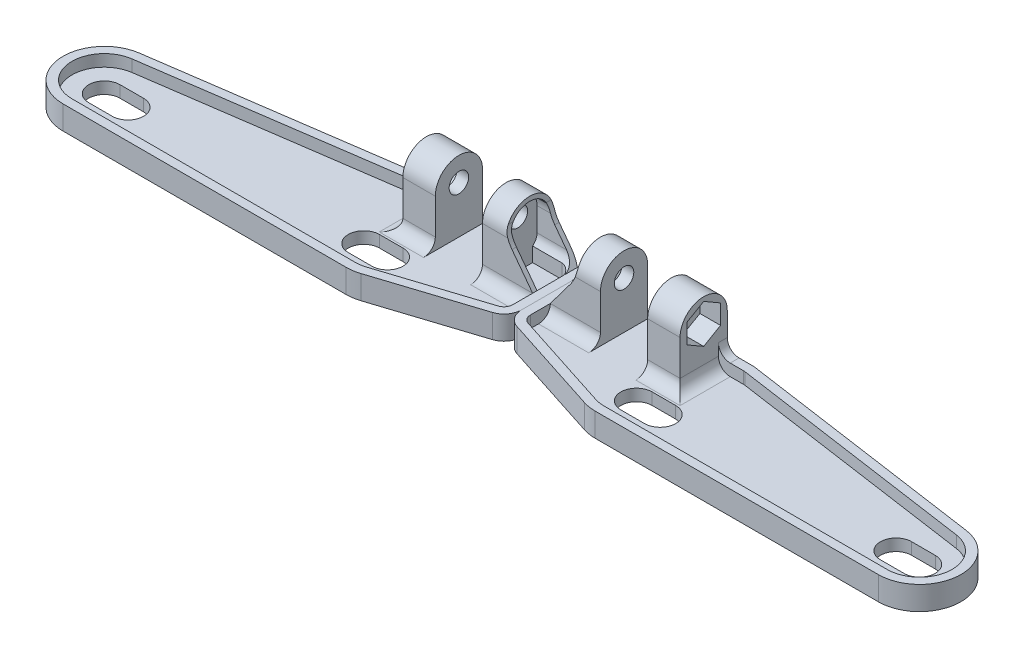
SolidWorks part; units mm, degrees
note: The reader was unsure of these and kept them because the rebuilt part matched: shared geometry of "Sketch2<3>".
ref_plane "Front Plane" through (0, 0, 0) normal (0, 0, 1) x (1, 0, 0)
ref_plane "Top Plane" through (0, 0, 0) normal (0, 1, 0) x (1, 0, 0)
ref_plane "Right Plane" through (0, 0, 0) normal (1, 0, 0) x (0, 0, -1)
sketch "Sketch2" plane through (0, 0, 0) normal (1, 0, 0) x (0, 0, -1)
  line L0 (4, 0) -> (4, -8)
  line L1 (4, -8) -> (-4, -8)
  line L2 (-4, -8) -> (-4, 0)
  line L4 (4, -8) -> (-16, -8)
  line L5 (4, -8) -> (4, -10)
  line L6 (4, -10) -> (-16, -10)
  line L7 (-16, -8) -> (-16, -10)
  circle A0 centre (0, 0) radius 4
  circle A1 centre (0, 0) radius 1.65
  dimension "D1" = 3.3
  dimension "D2" = 8
  dimension "D3" = 20
  dimension "D4" = 2
  dimension "D5" = 8
extrude "Boss-Extrude1" add sketch "Sketch2" along normal mid plane 12 contours A0 A1
sketch "Sketch18" plane through (0, 0, 0) normal (0, 1, 0) x (1, 0, 0)
  line L1 (-6, 106.0892) -> (-6, -15.5384) construction
  line L3 (-6, 1.65) -> (-6, -1.65) construction
  line L5 (-31.1122, 87.1949) -> (-31.1122, 25.8498) construction
extrude "Boss-Extrude2" add sketch "Sketch2<3>" along normal mid plane 12 from offset 0 contours A0 L2 L1 L0
sketch "Sketch2<3>" plane through (0, 0, 0) normal (1, 0, 0) x (0, 0, -1) same geometry as "Sketch2"
ref_plane "Plane2" through (0, -8, 0) normal (0, -1, 0) x (-1, 0, 0)
sketch "Sketch14" plane through (0, -8, 0) normal (0, 1, 0) x (1, 0, 0)
  line L0 (0, 4) -> (-14, 4)
  line L1 (6, 4) -> (-6, 4) construction
  line L2 (-31.1122, 87.1949) -> (-31.1122, 25.8498) construction
  line L4 (-31.1122, -9) -> (-31.1122, 4) construction
  line L5 (-31.1122, 4) -> (-14, 4) construction
  line L7 (-53.1122, -9) -> (-9.1122, -9) construction
  line L9 (-56.1111, -2.0716) -> (-14, 4)
  line L10 (-55.1122, -16) -> (-7.1122, -16)
  line L11 (-4.963, -15.6619) -> (14, -9.5443)
  line L12 (-55.1122, -9) -> (-51.1122, -9) construction
  line L13 (-55.1122, -6.35) -> (-51.1122, -6.35)
  line L14 (-55.1122, -11.65) -> (-51.1122, -11.65)
  line L15 (-7.1122, -9) -> (-11.1122, -9) construction
  line L16 (-7.1122, -11.65) -> (-11.1122, -11.65)
  line L17 (-7.1122, -6.35) -> (-11.1122, -6.35)
  line L19 (14, -9.5443) -> (14, 4)
  line L20 (14, 4) -> (-14, 4)
  circle A0 centre (-53.1122, -9) radius 2.65 construction
  circle A1 centre (-9.1122, -9) radius 2.65 construction
  arc A3 (-55.1122, -6.35) -> (-55.1122, -11.65) centre (-55.1122, -9) ccw
  arc A4 (-51.1122, -11.65) -> (-51.1122, -6.35) centre (-51.1122, -9) ccw
  arc A5 (-7.1122, -11.65) -> (-7.1122, -6.35) centre (-7.1122, -9) ccw
  arc A6 (-11.1122, -6.35) -> (-11.1122, -11.65) centre (-11.1122, -9) ccw
  circle A7 centre (-7.1122, -9) radius 7
  circle A8 centre (-55.1122, -9) radius 7
  point P15 (-31.1122, -9)
  point P28 (-53.1122, -9)
  point P35 (-9.1122, -9)
  dimension "D3" = 5.3
  dimension "14" = 14
  dimension "D1" = 8
  dimension "D2" = 44
  dimension "D4" = 13
  dimension "D6" = 4
  dimension "D7" = 4
  dimension "D9" = 8
extrude "Boss-Extrude7" add sketch "Sketch14" against normal blind 2 contours A7 A6 L17 A5 L16 | A7 A6 L16 A5 L17 | L10 A8 A4 L9 L0 L20 L19 L11 A7 A6
sketch "Sketch3" plane through (0, 0, 4) normal (0, 0, 1) x (1, 0, 0)
  line L1 (-4, 8) -> (4, 8)
  line L2 (-4, 8) -> (-4, -8)
  line L3 (-4, -8) -> (4, -8)
  line L4 (4, 8) -> (4, -8)
  line L5 (-4, 8) -> (4, -8) construction
  line L6 (-4, -8) -> (4, 8) construction
  line L7 (6, -8) -> (6, 0) construction
  point P0 (0, 0)
  dimension "D1" = 2
extrude "Cut-Extrude1" cut sketch "Sketch3" against normal blind 20
ref_plane "Plane1" through (0, 0, 0) normal (1, 0, 0) x (0, 0, -1)
sketch "Sketch8" plane through (6, 0, 0) normal (1, 0, 0) x (0, 0, -1)
  line L0 (-4, 0) -> (-4, -8)
  line L1 (-4, -8) -> (4, -8)
  line L2 (4, -8) -> (4, 0)
  line L4 (0, -3.3) -> (2.8579, -1.65)
  line L5 (2.8579, -1.65) -> (2.8579, 1.65)
  line L6 (2.8579, 1.65) -> (0, 3.3)
  line L7 (0, 3.3) -> (-2.8579, 1.65)
  line L8 (-2.8579, 1.65) -> (-2.8579, -1.65)
  line L9 (-2.8579, -1.65) -> (0, -3.3)
  circle A0 centre (0, 0) radius 4
  circle A1 centre (0, 0) radius 2.8579 construction
  dimension "D1" = 3.3
extrude "Boss-Extrude5" add sketch "Sketch8" against normal blind 3.5 from surface
sketch "Sketch11" plane through (-6, 0, 0) normal (-1, 0, 0) x (0, 0, 1)
  line L0 (-4, 0) -> (-4, -8)
  line L1 (-4, -8) -> (4, -8)
  line L2 (4, -8) -> (4, 0)
  line L3 (3.25, 0) -> (3.25, -8)
  line L4 (-3.25, 0) -> (-3.25, -8)
  circle A0 centre (0, 0) radius 3.25
  circle A1 centre (0, 0) radius 4
  dimension "D1" = 6.5
extrude "Boss-Extrude6" add sketch "Sketch11" against normal blind 8 from surface
sketch "Sketch12" plane through (0, 0, 4) normal (0, 0, 1) x (1, 0, 0)
  line L0 (4, 4) -> (8, 4)
  line L1 (14, 0) -> (14, 4) construction
  line L2 (8, 4) -> (8, 0)
  line L4 (8, 0) -> (14, -8)
  line L5 (14, -8) -> (14, 4)
  line L7 (14, 4) -> (8, 4)
  line L8 (14, 0) -> (14, -8) construction
  line L9 (14, -8) -> (12.5, -8) construction
  line L10 (14, -8) -> (4, -8) construction
  line L11 (12.5, -8) -> (12.5, -6) construction
  dimension "D1" = 4
  dimension "D2" = 1.5
  dimension "D3" = 2
extrude "Cut-Extrude2" cut sketch "Sketch12" against normal through all
fillet "Fillet1" radius 5 2 edges at (8, 0, 3.625) (8, 0, -3.625)
sketch "Sketch16" plane through (0, -10, 0) normal (0, -1, 0) x (1, 0, 0)
  line L0 (-51.1122, 11.65) -> (-55.1122, 6.35) construction
  line L1 (-11.1122, 11.65) -> (-7.1122, 6.35) construction
  line L2 (-7.1122, 9) -> (-11.1122, 9) construction
  line L3 (-51.1122, 9) -> (-55.1122, 9) construction
  point P12 (-9.1122, 9)
  point P16 (-53.1122, 9)
fillet "Fillet2" radius 3 3 edges at (14, -9, -4) (-14, -9, -4) (14, -9, 9.5443)
sketch "Sketch19" plane through (0, -8, 0) normal (0, 1, 0) x (1, 0, 0)
  line L0 (-14.213, 3.9693) -> (-56.1111, -2.0716)
  line L1 (-55.1122, -16) -> (-7.1122, -16)
  line L2 (-4.963, -15.6619) -> (11.9211, -10.215)
  line L3 (14, -7.3599) -> (14, 1)
  line L5 (11, 4) -> (-8.5211, 4)
  line L6 (-8.5211, 4) -> (-13.7848, 4)
  line L7 (-13.9989, 2.4846) -> (-55.897, -3.5563)
  line L8 (-55.1122, -14.5) -> (-7.1122, -14.5)
  line L9 (-5.4235, -14.2344) -> (11.4605, -8.7874)
  line L10 (12.5, -7.3599) -> (12.5, 1)
  line L11 (11, 2.5) -> (-8.5211, 2.5)
  line L12 (-8.5211, 2.5) -> (-13.7848, 2.5)
  arc A0 (-56.1111, -2.0716) -> (-55.1122, -16) centre (-55.1122, -9) ccw
  arc A1 (-7.1122, -16) -> (-4.963, -15.6619) centre (-7.1122, -9) ccw
  arc A2 (11.9211, -10.215) -> (14, -7.3599) centre (11, -7.3599) ccw
  arc A4 (14, 1) -> (11, 4) centre (11, 1) ccw
  arc A13 (-14.213, 3.9693) -> (-13.7848, 4) centre (-13.7848, 1) cw
  arc A14 (-55.897, -3.5563) -> (-55.1122, -14.5) centre (-55.1122, -9) ccw
  arc A15 (-7.1122, -14.5) -> (-5.4235, -14.2344) centre (-7.1122, -9) ccw
  arc A16 (11.4605, -8.7874) -> (12.5, -7.3599) centre (11, -7.3599) ccw
  arc A17 (12.5, 1) -> (11, 2.5) centre (11, 1) ccw
  arc A18 (-13.9989, 2.4846) -> (-13.7848, 2.5) centre (-13.7848, 1) cw
extrude "Boss-Extrude8" add sketch "Sketch19" along normal blind 2
fillet "Fillet3" radius 2 5 edges at (9.25, -6, -3.25) (-9.5, -8, 0.75) (-6.75, -8, 4) (8.25, -8, 4) (-9.5, -6, -3.25)
ref_plane "Plane3" through (-31.1122, 0, 0) normal (-1, 0, 0) x (0, 0, 1)
sketch "Sketch23" plane through (0, 0, -2.5) normal (0, 0, 1) x (1, 0, 0)
  line L0 (4, -8) -> (-4, -8) construction
  line L1 (-4, -6) -> (4, -6)
  line L2 (-4, -6) -> (-4, -8)
  line L3 (-4, -8) -> (4, -8)
  line L4 (4, -6) -> (4, -8)
extrude "Cut-Extrude4" cut sketch "Sketch23" against normal blind 10
mirror "Mirror1" about plane through (14, -10, 0) normal (1, 0, 0) of bodies 119 113
sketch "Sketch20" plane through (0, -10, 0) normal (0, 1, 0) x (1, 0, 0)
  line L0 (34, 106.0892) -> (34, -15.5384) construction
  line L1 (14, 1) -> (14, 94.286) construction
  line L2 (59.1122, 90.7486) -> (59.1122, 29.4036) construction
  line L3 (-6, 45.2754) -> (34, 45.2754) construction
  line L4 (-6, 106.0892) -> (-6, -15.5384) construction
  line L5 (-31.1122, 87.1949) -> (-31.1122, 25.8498) construction
  line L8 (-31.1122, 37.6061) -> (59.1122, 37.6061) construction
  point P7 (14, 45.2754)
  point P20 (14, 37.6061)
sketch "Sketch21" plane through (0, -10, 0) normal (0, -1, 0) x (1, 0, 0)
  line L0 (35.1122, 6.35) -> (39.1122, 11.65) construction
  line L1 (79.1122, 6.35) -> (83.1122, 11.65) construction
  point P4 (37.1122, 9)
  point P11 (81.1122, 9)
  point P12 (93.637, 29.886)
